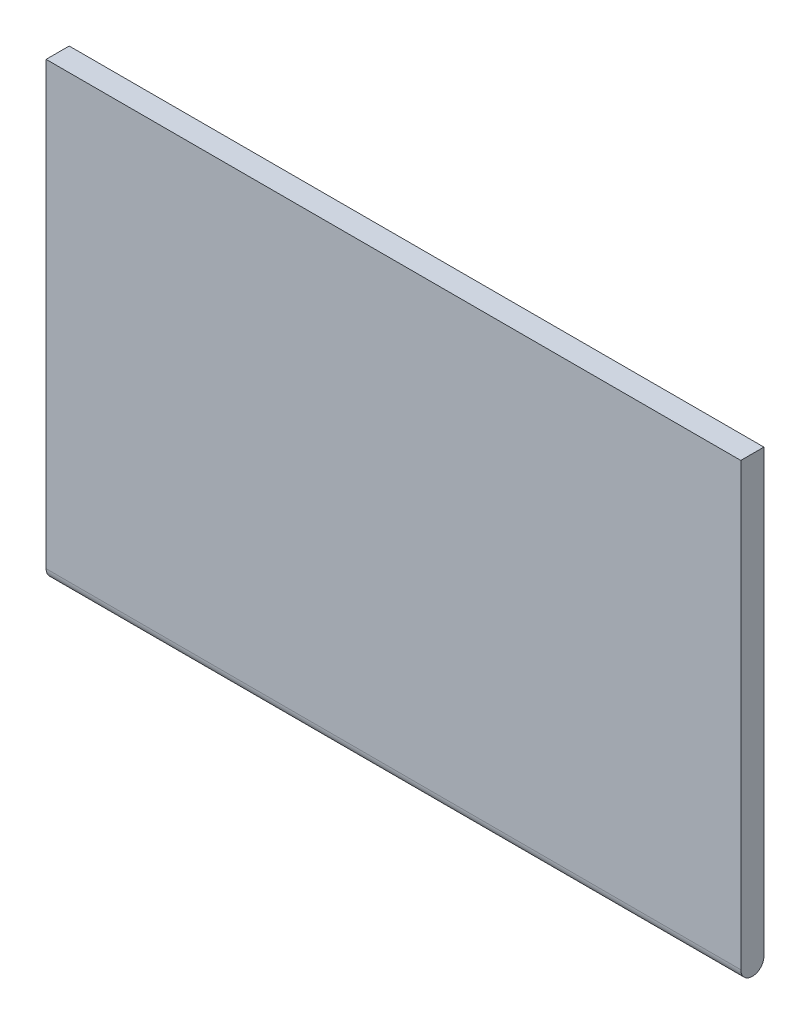
SolidWorks part; units mm, degrees
ref_plane "Front Plane" through (0, 0, 0) normal (0, 0, 1) x (1, 0, 0)
ref_plane "Top Plane" through (0, 0, 0) normal (0, 1, 0) x (1, 0, 0)
ref_plane "Right Plane" through (0, 0, 0) normal (1, 0, 0) x (0, 0, -1)
sketch "Sketch2" plane through (0, 0, 0) normal (0, 0, 1) x (1, 0, 0)
  line L1 (-191.008, -124.46) -> (191.008, -124.46)
  line L2 (-191.008, -124.46) -> (-191.008, 124.46)
  line L3 (-191.008, 124.46) -> (191.008, 124.46)
  line L4 (191.008, -124.46) -> (191.008, 124.46)
  line L5 (-191.008, -124.46) -> (191.008, 124.46) construction
  line L6 (-191.008, 124.46) -> (191.008, -124.46) construction
  point P0 (0, 0)
  dimension "D1" = 382.016
  dimension "D2" = 248.92
extrude "Boss-Extrude1" add sketch "Sketch2" along normal blind 12.7
fillet "Fillet1" radius 6.35 2 edges at (0, -124.46, 0) (0, -124.46, 12.7)
